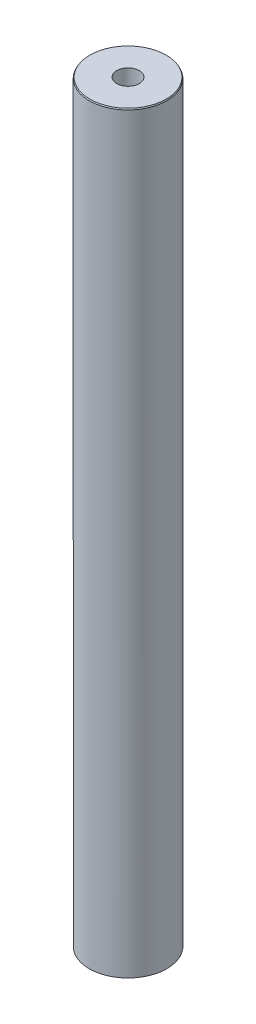
SolidWorks part; units mm, degrees
ref_plane "Front Plane" through (0, 0, 0) normal (0, 0, 1) x (1, 0, 0)
ref_plane "Top Plane" through (0, 0, 0) normal (0, 1, 0) x (1, 0, 0)
ref_plane "Right Plane" through (0, 0, 0) normal (1, 0, 0) x (0, 0, -1)
sketch "Sketch1" plane through (0, 0, 0) normal (0, 1, 0) x (1, 0, 0)
  circle A0 centre (0, 0) radius 7.5
  dimension "SHAFT_OD" = 15
extrude "Boss-Extrude1" add sketch "Sketch1" along normal blind 145.7484
sketch "Sketch2" plane through (0, 0, 0) normal (0, 1, 0) x (1, 0, 0)
  circle A0 centre (0, 0) radius 2.1804
  dimension "BORE_D" = 4.3609
extrude "Cut-Extrude1" cut sketch "Sketch2" along normal through all
chamfer "Chamfer1" distance 0.2085 angle 30 2 edges at (0, 145.7484, 7.5) (0, 0, 7.5) first distance on face at (0, 145.7484, 7.5) first distance on face at (0, 0, 2.1804)
